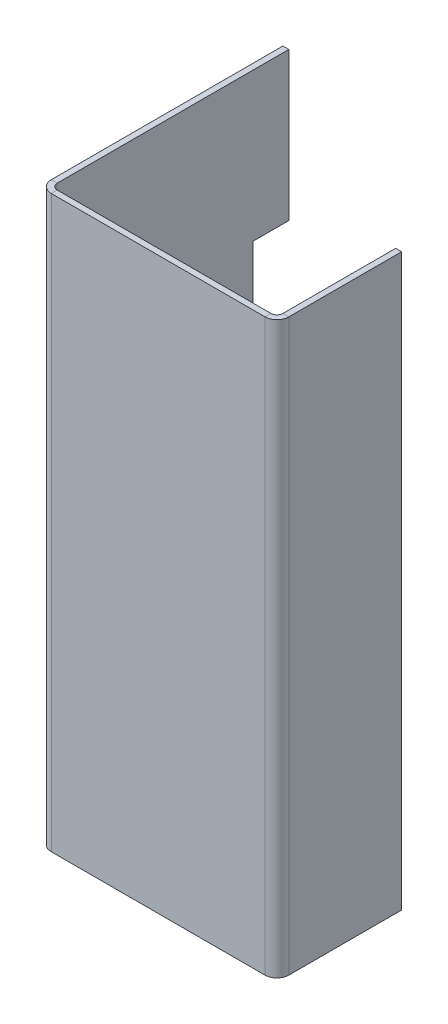
SolidWorks part; units mm, degrees
note: The reader was unsure of these and kept them because the rebuilt part matched: flange length of "Edge-Flange1", "Edge-Flange2".
material "6061 Alloy"
ref_plane "Front Plane" through (0, 0, 0) normal (0, 0, 1) x (1, 0, 0)
ref_plane "Top Plane" through (0, 0, 0) normal (0, 1, 0) x (1, 0, 0)
ref_plane "Right Plane" through (0, 0, 0) normal (1, 0, 0) x (0, 0, -1)
sketch "Sketch1" plane through (0, 0, 0) normal (0, 0, 1) x (1, 0, 0)
  line L1 (-31.75, -76.2) -> (31.75, -76.2)
  line L2 (-31.75, -76.2) -> (-31.75, 76.2)
  line L3 (-31.75, 76.2) -> (31.75, 76.2)
  line L4 (31.75, -76.2) -> (31.75, 76.2)
  line L5 (-31.75, -76.2) -> (31.75, 76.2) construction
  line L6 (-31.75, 76.2) -> (31.75, -76.2) construction
  point P0 (0, 0)
  dimension "D1" = 63.5
  dimension "D2" = 152.4
base flange "Base-Flange1" sketch "Sketch1" thickness 1.5875 reverse thickness direction no parameters "D1"=254
edge flange "Edge-Flange1" sketch "Sketch8" flange angle 90 flange length 31.75 flange position material inside bend radius 1.5875 thickness 1.5875 relief rectangular parameters "D6"=10
sketch "Sketch8" plane through (31.75, 0, -1.5875) normal (-1, 0, 0) x (0, 1, 0)
  line L1 (76.2, 0) -> (-76.2, 0) construction
  line L2 (-76.2, 0) -> (-76.2, 31.75)
  line L3 (-76.2, 31.75) -> (76.2, 31.75)
  line L4 (76.2, 31.75) -> (76.2, 0)
  line L5 (76.2, 0) -> (-76.2, 0)
bend "EdgeBend1" bend radius 1.5875 bend angle 90 parameters "D5"=1
edge flange "Edge-Flange2" sketch "Sketch11" flange angle 90 flange length 63.5 flange position material inside bend radius 1.5875 thickness 1.5875 relief rectangular parameters "D6"=10
sketch "Sketch11" plane through (-31.75, 0, -1.5875) normal (1, 0, 0) x (0, -1, 0)
  line L1 (76.2, 0) -> (-76.2, 0) construction
  line L2 (-76.2, 0) -> (-76.2, 63.5)
  line L3 (-76.2, 63.5) -> (76.2, 63.5)
  line L4 (76.2, 63.5) -> (76.2, 0)
  line L5 (76.2, 0) -> (-76.2, 0)
bend "EdgeBend2" bend radius 1.5875 bend angle 90 parameters "D5"=2
sketch "Sketch12" plane through (-31.75, 0, 0) normal (-1, 0, 0) x (0, 0, 1)
  line L0 (-9.525, -76.2) -> (-9.525, 76.2) construction
  line L1 (-3.175, -76.2) -> (-65.0875, -76.2) construction
  line L2 (-65.0875, 76.2) -> (-3.175, 76.2) construction
  line L3 (0, 76.2) -> (0, -76.2) construction
  point P8 (-9.525, -50.8)
  point P9 (-9.525, 0)
  point P10 (-9.525, 50.8)
  dimension "D1" = 9.525
  dimension "D2" = 25.4
  dimension "D3" = 50.8
  dimension "D4" = 50.8
hole_wizard "#4 Clearance Hole1" positions "Sketch14" profile "Sketch13" hole size "#4" standard "ANSI Inch"
sketch "Sketch14" plane through (-31.75, 0, 0) normal (-1, 0, 0) x (0, 0, 1)
  point P0 (-9.525, -50.8)
  point P3 (-9.525, 0)
  point P6 (-9.525, 50.8)
sketch "Sketch13" plane through (-31.75, -50.8, -9.525) normal (0, 1, 0) x (0, 0, 1)
  line L0 (0, 0) -> (0, 2.5671)
  line L1 (0, 2.5671) -> (1.6319, 1.5865)
  line L2 (1.6319, 1.5865) -> (1.6319, 0)
  line L5 (1.6319, 0) -> (0, 0)
  line L10 (0, 2.5671) -> (-1.632, 1.5865) construction
  line L11 (0, -6.35) -> (0, 107.95) construction
  dimension "Hole Dia." = 3.2639
  dimension "Hole Depth" = 1.5865
  dimension "Drill Angle" = 118
sketch "Sketch16" plane through (-30.1625, 0, 0) normal (1, 0, 0) x (0, 0, -1)
  line L0 (65.0875, -76.2) -> (65.0875, 76.2) construction
  line L1 (65.0875, 36.576) -> (55.5625, 36.576)
  line L2 (65.0875, 36.576) -> (65.0875, -45.974)
  line L3 (65.0875, -45.974) -> (55.5625, -45.974)
  line L4 (55.5625, 36.576) -> (55.5625, -45.974)
  line L6 (3.175, -76.2) -> (65.0875, -76.2) construction
  dimension "D1" = 9.525
  dimension "D2" = 30.226
  dimension "D3" = 82.55
extrude "Cut-Extrude1" cut sketch "Sketch16" against normal through all normal cut yes
sketch "Bend-Lines1" [suppressed] plane through (0, 0, 0) normal (0, 1, 0) x (1, 0, 0)
sketch "Bounding-Box1" [suppressed] plane through (0, 0, 0) normal (0, 1, 0) x (1, 0, 0)
sheet metal parameters "Sheet-Metal1" thickness 1.5875 parameters "D1"=254
flat pattern "Flat-Pattern1" [suppressed]
sketch "Bend-Lines2" plane through (0, 0, 0) normal (0, 1, 0) x (1, 0, 0)
sketch3d "Bounding-Box2" [suppressed]
  line L0 (-31.75, 76.2, 0) -> (-31.75, -76.2, 0) construction
  line L1 (31.75, 76.2, 0) -> (31.75, -76.2, 0) construction
  line L2 (-31.75, 76.2, 0) -> (31.75, 76.2, 0) construction
  line L3 (-31.75, -76.2, 0) -> (31.75, -76.2, 0) construction
sheet metal parameters "Sheet-Metal2" thickness 1.5875 parameters "D1"=254
flat pattern "Flat-Pattern1"
sketch "Bend-Lines2" plane through (0, 0, 0) normal (0, 0, 1) x (1, 0, 0)
  line L0 (30.4452, -76.2) -> (30.4452, 76.2) construction
  line L1 (30.4452, -76.2) -> (30.4452, 76.2) construction
sketch3d "Bounding-Box2" [suppressed]
  line L0 (62.478, 76.2, 0) -> (62.478, -76.2, 0) construction
  line L1 (-31.75, 76.2, 0) -> (-31.75, -76.2, 0) construction
  line L2 (62.478, 76.2, 0) -> (-31.75, 76.2, 0) construction
  line L3 (62.478, -76.2, 0) -> (-31.75, -76.2, 0) construction
bend of the flat pattern "Flatten-<EdgeBend1>1"
sheet metal parameters "Sheet-Metal3" thickness 1.5875 parameters "D1"=254
flat pattern "Flat-Pattern1"
sketch "Bend-Lines2" plane through (0, 0, 0) normal (0, 0, 1) x (1, 0, 0)
  line L0 (30.4452, -76.2) -> (30.4452, 76.2) construction
  line L1 (30.4452, -76.2) -> (30.4452, 76.2) construction
  line L2 (-30.4452, 76.2) -> (-30.4452, -76.2) construction
  line L3 (-30.4452, 76.2) -> (-30.4452, -76.2) construction
sketch3d "Bounding-Box2" [suppressed]
  line L0 (-94.228, -76.2, 0) -> (62.478, -76.2, 0) construction
  line L1 (-94.228, 76.2, 0) -> (62.478, 76.2, 0) construction
  line L2 (-94.228, -76.2, 0) -> (-94.228, 76.2, 0) construction
  line L3 (62.478, -76.2, 0) -> (62.478, 76.2, 0) construction
bend of the flat pattern "Flatten-<EdgeBend1>1"
bend of the flat pattern "Flatten-<EdgeBend2>1"
sheet metal parameters "Sheet-Metal4" thickness 1.5875 parameters "D1"=254
flat pattern "Flat-Pattern1" [suppressed]
sketch "Bend-Lines2" plane through (0, 0, 0) normal (0, 0, 1) x (1, 0, 0)
  line L0 (30.4452, -76.2) -> (30.4452, 76.2) construction
  line L1 (30.4452, -76.2) -> (30.4452, 76.2) construction
  line L2 (-30.4452, 76.2) -> (-30.4452, -76.2) construction
  line L3 (-30.4452, 76.2) -> (-30.4452, -76.2) construction
sketch3d "Bounding-Box2" [suppressed]
  line L0 (-94.228, -76.2, 0) -> (62.478, -76.2, 0) construction
  line L1 (-94.228, 76.2, 0) -> (62.478, 76.2, 0) construction
  line L2 (-94.228, -76.2, 0) -> (-94.228, 76.2, 0) construction
  line L3 (62.478, -76.2, 0) -> (62.478, 76.2, 0) construction
bend of the flat pattern "Flatten-<EdgeBend1>1"
bend of the flat pattern "Flatten-<EdgeBend2>1"
sketch "Sketch12-1" [suppressed] plane through (-29.1405, 0, 0) normal (0, 0, 1) x (1, 0, 0)
  line L0 (-9.525, -76.2) -> (-9.525, 76.2) construction
  line L3 (0, 76.2) -> (0, -76.2) construction
  point P8 (-9.525, -50.8)
  point P9 (-9.525, 0)
  point P10 (-9.525, 50.8)
  dimension "D1" = 9.525
  dimension "D2" = 25.4
  dimension "D3" = 50.8
  dimension "D4" = 50.8
sheet metal parameters "Sheet-Metal5" thickness 1.5875 parameters "D1"=254
flat pattern "Flat-Pattern1" [suppressed]
sketch "Bend-Lines2" plane through (0, 0, 0) normal (0, 0, 1) x (1, 0, 0)
  line L0 (30.4452, -76.2) -> (30.4452, 76.2) construction
  line L1 (30.4452, -76.2) -> (30.4452, 76.2) construction
  line L2 (-30.4452, 76.2) -> (-30.4452, -76.2) construction
  line L3 (-30.4452, 76.2) -> (-30.4452, -76.2) construction
sketch3d "Bounding-Box2" [suppressed]
  line L0 (-94.228, -76.2, 0) -> (62.478, -76.2, 0) construction
  line L1 (-94.228, 76.2, 0) -> (62.478, 76.2, 0) construction
  line L2 (-94.228, -76.2, 0) -> (-94.228, 76.2, 0) construction
  line L3 (62.478, -76.2, 0) -> (62.478, 76.2, 0) construction
bend of the flat pattern "Flatten-<EdgeBend1>1"
bend of the flat pattern "Flatten-<EdgeBend2>1"
sketch "Sketch12-1" [suppressed] plane through (-29.1405, 0, 0) normal (0, 0, 1) x (1, 0, 0)
  line L0 (-9.525, -76.2) -> (-9.525, 76.2) construction
  line L3 (0, 76.2) -> (0, -76.2) construction
  point P8 (-9.525, -50.8)
  point P9 (-9.525, 0)
  point P10 (-9.525, 50.8)
  dimension "D1" = 9.525
  dimension "D2" = 25.4
  dimension "D3" = 50.8
  dimension "D4" = 50.8
